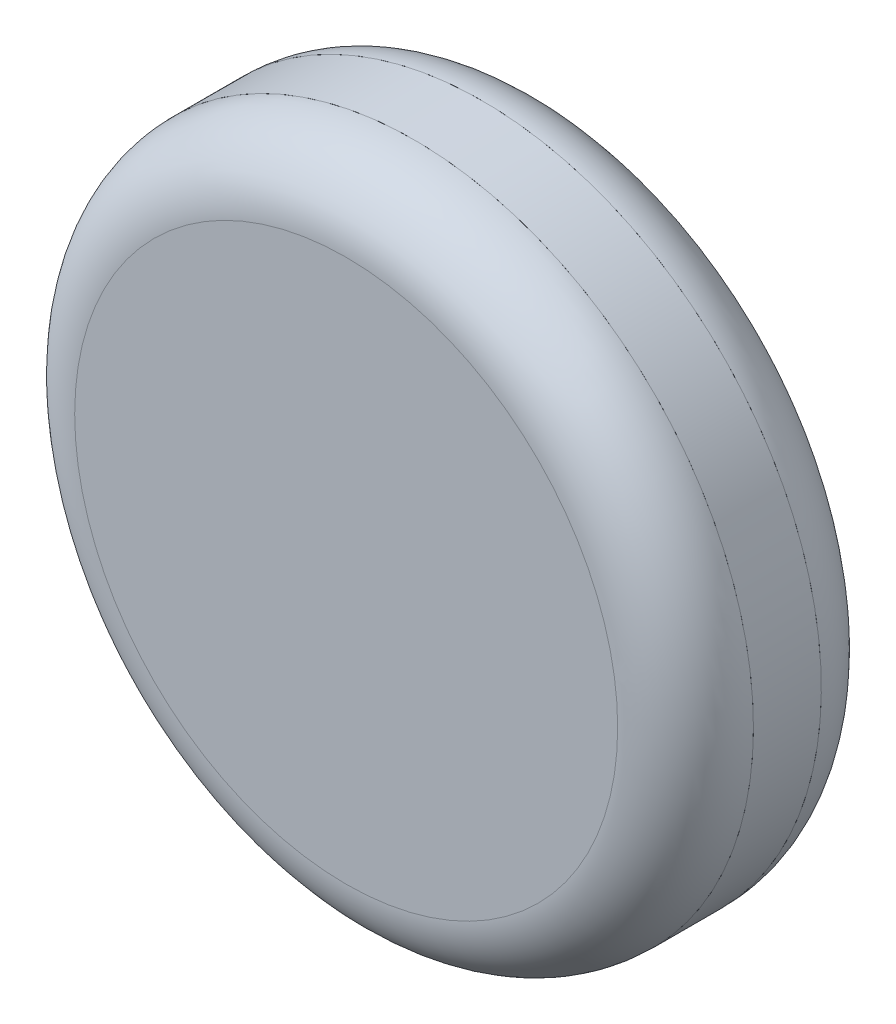
SolidWorks part; units mm, degrees
ref_plane "Front Plane" through (0, 0, 0) normal (0, 0, 1) x (1, 0, 0)
ref_plane "Top Plane" through (0, 0, 0) normal (0, 1, 0) x (1, 0, 0)
ref_plane "Right Plane" through (0, 0, 0) normal (1, 0, 0) x (0, 0, -1)
sketch "Sketch1" plane through (0, 0, 0) normal (0, 0, 1) x (1, 0, 0)
  line L0 (0, 17.3966) -> (0, -20.9217) construction
  line L1 (0, -15) -> (0, 0) construction
  line L2 (-1.5, -15) -> (-1.5, 0)
  line L3 (1.5, -15) -> (1.5, 0)
  circle A0 centre (0, 0) radius 10
  arc A1 (-1.5, -15) -> (1.5, -15) centre (0, -15) ccw
  arc A2 (1.5, 0) -> (-1.5, 0) centre (0, 0) ccw
  point P6 (0, -7.5)
  dimension "D1" = 20
  dimension "D2" = 3
  dimension "D3" = 15
extrude "Boss-Extrude1" add sketch "Sketch1" along normal blind 2 contours A2 L3 A0 L2 region at (-6.3353, 7.369, 0)
sketch "Sketch2" plane through (0, 0, 2) normal (0, 0, 1) x (1, 0, 0)
  circle A0 centre (0, 0) radius 10
  arc A3 (1.5, -9.8869) -> (-1.5, -9.8869) centre (0, 0) ccw construction
extrude "Boss-Extrude2" add sketch "Sketch2" along normal blind 2 separate body
sketch "Sketch3" plane through (0, 0, 0) normal (0, 0, -1) x (-1, 0, 0)
  circle A0 centre (0, 0) radius 10
  arc A1 (1.5, -9.8869) -> (-1.5, -9.8869) centre (0, 0) ccw construction
extrude "Boss-Extrude3" add sketch "Sketch3" along normal blind 2 separate body
fillet "Fillet2" radius 2 1 edges at (-10, 0, -2)
fillet "Fillet3" radius 2 1 edges at (10, 0, 4)
